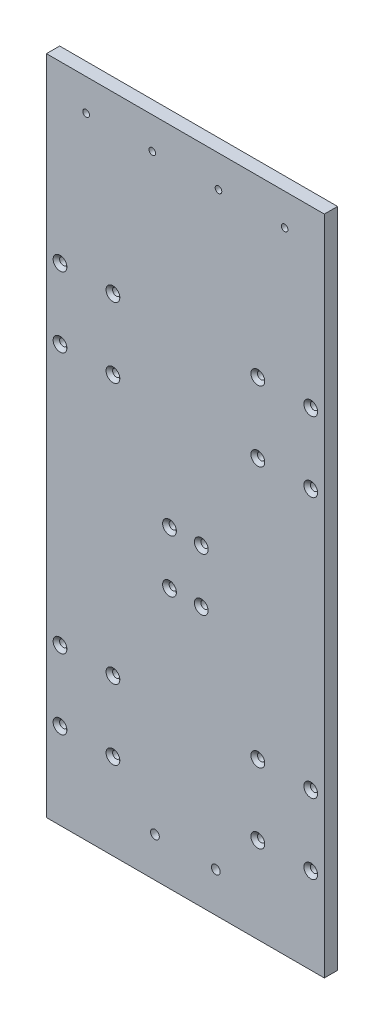
SolidWorks part; units mm, degrees
note: The reader was unsure of these and kept them because the rebuilt part matched: thickness of "Base-Flange1", "Sheet-Metal1", "Sheet-Metal2", "Sheet-Metal3", "Sheet-Metal4", "Sheet-Metal5", "Sheet-Metal6", "Sheet-Metal7", "Sheet-Metal8".
ref_plane "Front Plane" through (0, 0, 0) normal (0, 0, 1) x (1, 0, 0)
ref_plane "Top Plane" through (0, 0, 0) normal (0, 1, 0) x (1, 0, 0)
ref_plane "Right Plane" through (0, 0, 0) normal (1, 0, 0) x (0, 0, -1)
sketch "Sketch1" plane through (0, 0, 0) normal (0, 0, 1) x (1, 0, 0)
  line L1 (-105, -250) -> (105, -250)
  line L2 (-105, -250) -> (-105, 250)
  line L3 (-105, 250) -> (105, 250)
  line L4 (105, -250) -> (105, 250)
  line L5 (-105, -250) -> (105, 250) construction
  line L6 (-105, 250) -> (105, -250) construction
  point P0 (0, 0)
  dimension "D1" = 210
  dimension "D2" = 500
base flange "Base-Flange1" sketch "Sketch1" thickness 10 reverse thickness direction no parameters "D1"=2
sketch "Sketch2" plane through (0, 0, 0) normal (0, 0, 1) x (1, 0, 0)
  line L0 (-74.75, 91.5) -> (74.75, 91.5) construction
  line L1 (-94.75, 65) -> (-54.75, 65) construction
  line L2 (-94.75, 65) -> (-94.75, 118) construction
  line L3 (-94.75, 118) -> (-54.75, 118) construction
  line L4 (-54.75, 65) -> (-54.75, 118) construction
  line L5 (-94.75, 65) -> (-54.75, 118) construction
  line L6 (-94.75, 118) -> (-54.75, 65) construction
  line L7 (54.75, 65) -> (94.75, 65) construction
  line L8 (54.75, 65) -> (54.75, 118) construction
  line L9 (54.75, 118) -> (94.75, 118) construction
  line L10 (94.75, 65) -> (94.75, 118) construction
  line L11 (54.75, 65) -> (94.75, 118) construction
  line L12 (54.75, 118) -> (94.75, 65) construction
  line L13 (-94.75, -185) -> (-54.75, -185) construction
  line L14 (-94.75, -185) -> (-94.75, -132) construction
  line L15 (-94.75, -132) -> (-54.75, -132) construction
  line L16 (-54.75, -185) -> (-54.75, -132) construction
  line L17 (-94.75, -185) -> (-54.75, -132) construction
  line L18 (-94.75, -132) -> (-54.75, -185) construction
  line L19 (54.75, -185) -> (94.75, -185) construction
  line L20 (54.75, -185) -> (54.75, -132) construction
  line L21 (54.75, -132) -> (94.75, -132) construction
  line L22 (94.75, -185) -> (94.75, -132) construction
  line L23 (54.75, -185) -> (94.75, -132) construction
  line L24 (54.75, -132) -> (94.75, -185) construction
  line L25 (74.75, 91.5) -> (74.75, -158.5) construction
  line L26 (74.75, -158.5) -> (-74.75, -158.5) construction
  line L27 (0, 91.5) -> (0, 250) construction
  line L28 (105, 250) -> (-105, 250) construction
  line L29 (-74.75, -158.5) -> (-74.75, 91.5) construction
  circle A0 centre (-94.75, 118) radius 2.75
  circle A1 centre (-94.75, 65) radius 2.75
  circle A2 centre (-54.75, 118) radius 2.75
  circle A3 centre (-54.75, 65) radius 2.75
  circle A4 centre (54.75, 118) radius 2.75
  circle A5 centre (54.75, 65) radius 2.75
  circle A6 centre (94.75, 118) radius 2.75
  circle A7 centre (94.75, 65) radius 2.75
  circle A8 centre (-54.75, -132) radius 2.75
  circle A9 centre (-94.75, -132) radius 2.75
  circle A10 centre (-94.75, -185) radius 2.75
  circle A11 centre (-54.75, -185) radius 2.75
  circle A12 centre (54.75, -132) radius 2.75
  circle A13 centre (94.75, -132) radius 2.75
  circle A14 centre (94.75, -185) radius 2.75
  circle A15 centre (54.75, -185) radius 2.75
  point P0 (-74.75, 91.5)
  point P5 (74.75, 91.5)
  point P10 (-74.75, -158.5)
  point P15 (74.75, -158.5)
  dimension "D3" = 5.5
  dimension "D4" = 189.5
  dimension "D5" = 303
  dimension "D6" = 132
  dimension "D1" = 40
  dimension "D2" = 53
extrude "Cut-Extrude1" cut sketch "Sketch2" against normal blind 10
sketch "Sketch3" plane through (0, 0, 0) normal (0, 0, 1) x (1, 0, 0)
  line L0 (-23, -220) -> (23, -220) construction
  line L1 (0, -220) -> (0, -250) construction
  line L2 (-105, -250) -> (105, -250) construction
  circle A0 centre (-23, -220) radius 3.3
  circle A1 centre (23, -220) radius 3.3
  dimension "D1" = 6.6
  dimension "D2" = 46
  dimension "D3" = 30
extrude "Cut-Extrude2" cut sketch "Sketch3" against normal blind 10
sketch "Sketch4" plane through (0, 0, 0) normal (0, 0, 1) x (1, 0, 0)
  line L0 (-54.75, 65) -> (54.75, 65) construction
  line L1 (54.75, 65) -> (54.75, -132) construction
  line L2 (54.75, -132) -> (-54.75, -132) construction
  line L3 (-54.75, -132) -> (-54.75, 65) construction
  line L4 (0, -33.5) -> (54.75, -33.5) construction
  line L5 (-12, -53.5) -> (12, -53.5) construction
  line L6 (-12, -53.5) -> (-12, -13.5) construction
  line L7 (-12, -13.5) -> (12, -13.5) construction
  line L8 (12, -53.5) -> (12, -13.5) construction
  line L9 (-12, -53.5) -> (12, -13.5) construction
  line L10 (-12, -13.5) -> (12, -53.5) construction
  line L11 (0, -33.5) -> (0, 65) construction
  circle A0 centre (12, -13.5) radius 2.75
  circle A1 centre (12, -53.5) radius 2.75
  circle A2 centre (-12, -53.5) radius 2.75
  circle A3 centre (-12, -13.5) radius 2.75
  point P6 (0, -33.5)
  dimension "D3" = 5.5
  dimension "D1" = 24
  dimension "D2" = 40
extrude "Cut-Extrude3" cut sketch "Sketch4" against normal blind 10
sketch "Sketch5" plane through (0, 0, -10) normal (0, 0, -1) x (-1, 0, 0)
  line L0 (-75, 226) -> (75, 226) construction
  line L1 (0, 226) -> (0, 250) construction
  line L2 (-105, 250) -> (105, 250) construction
  circle A0 centre (-75, 226) radius 1.5
  circle A1 centre (-25, 226) radius 1.5
  circle A2 centre (25, 226) radius 1.5
  circle A3 centre (75, 226) radius 1.5
  dimension "D3" = 3
  dimension "D1" = 150
  dimension "D2" = 24
  dimension "D4" = 50
  dimension "D5" = 50
extrude "Cut-Extrude4" [suppressed] cut sketch "Sketch5" against normal through all
hole_wizard "M6x1.0 Tapped Hole1" positions "Sketch6" profile "Sketch7" tap size "M6x1.0" standard "ANSI Metric"
sketch "Sketch6" plane through (0, 0, -10) normal (0, 0, -1) x (-1, 0, 0)
  point P0 (-75, 226)
  point P3 (-25, 226)
  point P6 (25, 226)
  point P9 (75, 226)
sketch "Sketch7" plane through (75, 226, -10) normal (1, 0, 0) x (0, 1, 0)
  line L0 (0, 0) -> (0, 16.5022)
  line L1 (0, 16.5022) -> (2.5, 15)
  line L2 (2.5, 15) -> (2.5, 0.525)
  line L3 (2.5, 0.525) -> (3.025, 0)
  line L5 (3.025, 0) -> (0, 0)
  line L6 (-2.5, 0.525) -> (-3.025, 0) construction
  line L10 (0, 16.5022) -> (-2.5, 15) construction
  line L11 (0, -6.35) -> (0, 107.95) construction
  dimension "Tap Drill Dia." = 5
  dimension "Tap Drill Depth" = 15
  dimension "Near C'Sink Dia." = 6.05
  dimension "Near C'Sink Angle" = 90
  dimension "Drill Angle" = 118
hole_wizard "CSK for M5 Flat Head Machine Screw1" positions "Sketch8" profile "Sketch9" countersink size "M5" standard "ANSI Metric"
sketch "Sketch8" plane through (0, 0, 0) normal (0, 0, -1) x (-1, 0, 0)
  point P0 (-54.75, 118)
  point P3 (-94.75, 118)
  point P6 (-94.75, 65)
  point P9 (-54.75, 65)
  point P12 (54.75, 118)
  point P15 (94.75, 118)
  point P18 (54.75, 65)
  point P21 (94.75, 65)
  point P24 (-94.75, -132)
  point P27 (-54.75, -132)
  point P30 (-94.75, -185)
  point P33 (-54.75, -185)
  point P36 (54.75, -132)
  point P39 (54.75, -185)
  point P42 (94.75, -132)
  point P45 (94.75, -185)
sketch "Sketch9" plane through (54.75, 118, 0) normal (1, 0, 0) x (0, -1, 0)
  line L0 (0, 0) -> (0, 26.1524)
  line L1 (0, 26.1524) -> (2.75, 24.5)
  line L2 (2.75, 24.5) -> (2.75, 2.45)
  line L3 (2.75, 2.45) -> (5.2, 0)
  line L5 (5.2, 0) -> (0, 0)
  line L6 (-2.75, 2.45) -> (-5.2, 0) construction
  line L10 (0, 26.1524) -> (-2.75, 24.5) construction
  line L11 (0, -6.35) -> (0, 107.95) construction
  dimension "Hole Dia." = 5.5
  dimension "Hole Depth" = 24.5
  dimension "Near C'Sink Dia." = 10.4
  dimension "Near C'Sink Angle" = 90
  dimension "Drill Angle" = 118
hole_wizard "CSK for M5 Flat Head Machine Screw2" positions "Sketch10" profile "Sketch11" countersink size "M5" standard "ANSI Metric"
sketch "Sketch10" plane through (0, 0, 0) normal (0, 0, 1) x (1, 0, 0)
  point P0 (12, -13.5)
  point P3 (-12, -13.5)
  point P6 (-12, -53.5)
  point P9 (12, -53.5)
sketch "Sketch11" plane through (12, -13.5, 0) normal (1, 0, 0) x (0, -1, 0)
  line L0 (0, 0) -> (0, 26.1524)
  line L1 (0, 26.1524) -> (2.75, 24.5)
  line L2 (2.75, 24.5) -> (2.75, 2.45)
  line L3 (2.75, 2.45) -> (5.2, 0)
  line L5 (5.2, 0) -> (0, 0)
  line L6 (-2.75, 2.45) -> (-5.2, 0) construction
  line L10 (0, 26.1524) -> (-2.75, 24.5) construction
  line L11 (0, -6.35) -> (0, 107.95) construction
  dimension "Hole Dia." = 5.5
  dimension "Hole Depth" = 24.5
  dimension "Near C'Sink Dia." = 10.4
  dimension "Near C'Sink Angle" = 90
  dimension "Drill Angle" = 118
sketch "Sketch12" plane through (0, 0, 0) normal (0, 0, 1) x (1, 0, 0)
  line L0 (-70, -187) -> (-70, -207)
  line L1 (-70, -207) -> (-50, -207)
  line L2 (-105, 250) -> (-105, -250) construction
  line L3 (-105, -250) -> (105, -250) construction
  line L4 (0, 0) -> (0, -170.6801) construction
  line L5 (70, -207) -> (50, -207)
  line L6 (70, -187) -> (70, -207)
  dimension "D1" = 35
  dimension "D2" = 43
  dimension "D3" = 20
  dimension "D4" = 20
sketch "Bend-Lines1" [suppressed] plane through (0, 0, 0) normal (0, 1, 0) x (1, 0, 0)
sketch "Bounding-Box1" [suppressed] plane through (0, 0, 0) normal (0, 1, 0) x (1, 0, 0)
sheet metal parameters "Sheet-Metal1" thickness 10 parameters "D1"=2, "D7"=15
flat pattern "Flat-Pattern1" [suppressed]
sketch "Bend-Lines2" plane through (0, 0, 0) normal (0, 1, 0) x (1, 0, 0)
sketch3d "Bounding-Box2" [suppressed]
  line L0 (100, 250, 0) -> (100, -250, 0) construction
  line L1 (-100, 250, 0) -> (-100, -250, 0) construction
  line L2 (100, 250, 0) -> (-100, 250, 0) construction
  line L3 (100, -250, 0) -> (-100, -250, 0) construction
sheet metal parameters "Sheet-Metal2" thickness 10 parameters "D1"=2, "D7"=15
flat pattern "Flat-Pattern1"
sketch "Bend-Lines2" plane through (0, 0, 0) normal (0, 1, 0) x (1, 0, 0)
sketch3d "Bounding-Box2" [suppressed]
  line L0 (105, 250, 0) -> (105, -250, 0) construction
  line L1 (-105, 250, 0) -> (-105, -250, 0) construction
  line L2 (105, 250, 0) -> (-105, 250, 0) construction
  line L3 (105, -250, 0) -> (-105, -250, 0) construction
sheet metal parameters "Sheet-Metal3" thickness 10 parameters "D1"=2, "D7"=15
flat pattern "Flat-Pattern1"
sketch "Bend-Lines2" plane through (0, 0, 0) normal (0, 1, 0) x (1, 0, 0)
sketch3d "Bounding-Box2" [suppressed]
  line L0 (105, 250, 0) -> (105, -250, 0) construction
  line L1 (-105, 250, 0) -> (-105, -250, 0) construction
  line L2 (105, 250, 0) -> (-105, 250, 0) construction
  line L3 (105, -250, 0) -> (-105, -250, 0) construction
sheet metal parameters "Sheet-Metal4" thickness 10 parameters "D1"=2, "D7"=15
flat pattern "Flat-Pattern1" [suppressed]
sketch "Bend-Lines2" plane through (0, 0, 0) normal (0, 1, 0) x (1, 0, 0)
sketch3d "Bounding-Box2" [suppressed]
  line L0 (105, 250, 0) -> (105, -250, 0) construction
  line L1 (-105, 250, 0) -> (-105, -250, 0) construction
  line L2 (105, 250, 0) -> (-105, 250, 0) construction
  line L3 (105, -250, 0) -> (-105, -250, 0) construction
sketch "Sketch5-2" plane through (0, 0, -10) normal (0, 0, -1) x (-1, 0, 0)
  line L0 (-75, 226) -> (75, 226) construction
  line L1 (0, 226) -> (0, 250) construction
  line L2 (-105, 250) -> (105, 250) construction
  circle A0 centre (-75, 226) radius 3 construction
  circle A1 centre (-25, 226) radius 3 construction
  circle A2 centre (25, 226) radius 3 construction
  circle A3 centre (75, 226) radius 3 construction
  dimension "D3" = 6
  dimension "D1" = 150
  dimension "D2" = 24
  dimension "D4" = 50
  dimension "D5" = 50
sheet metal parameters "Sheet-Metal5" thickness 10 parameters "D1"=2, "D7"=15
flat pattern "Flat-Pattern1" [suppressed]
sketch "Bend-Lines2" plane through (0, 0, 0) normal (0, 1, 0) x (1, 0, 0)
sketch3d "Bounding-Box2" [suppressed]
  line L0 (105, 250, 0) -> (105, -250, 0) construction
  line L1 (-105, 250, 0) -> (-105, -250, 0) construction
  line L2 (105, 250, 0) -> (-105, 250, 0) construction
  line L3 (105, -250, 0) -> (-105, -250, 0) construction
sketch "Sketch5-1" [suppressed] plane through (0, 0, -10) normal (0, 0, -1) x (-1, 0, 0)
  line L0 (-75, 226) -> (75, 226) construction
  line L1 (0, 226) -> (0, 250) construction
  line L2 (-105, 250) -> (105, 250) construction
  circle A0 centre (-75, 226) radius 1.5
  circle A1 centre (-25, 226) radius 1.5
  circle A2 centre (25, 226) radius 1.5
  circle A3 centre (75, 226) radius 1.5
  dimension "D3" = 3
  dimension "D1" = 150
  dimension "D2" = 24
  dimension "D4" = 50
  dimension "D5" = 50
sheet metal parameters "Sheet-Metal6" thickness 10 parameters "D1"=2, "D7"=15
flat pattern "Flat-Pattern1" [suppressed]
sketch "Bend-Lines2" plane through (0, 0, 0) normal (0, 1, 0) x (1, 0, 0)
sketch3d "Bounding-Box2" [suppressed]
  line L0 (105, 250, 0) -> (105, -250, 0) construction
  line L1 (-105, 250, 0) -> (-105, -250, 0) construction
  line L2 (105, 250, 0) -> (-105, 250, 0) construction
  line L3 (105, -250, 0) -> (-105, -250, 0) construction
sketch "Sketch5-2" [suppressed] plane through (0, 0, -10) normal (0, 0, -1) x (-1, 0, 0)
  line L0 (-75, 226) -> (75, 226) construction
  line L1 (0, 226) -> (0, 250) construction
  line L2 (-105, 250) -> (105, 250) construction
  circle A0 centre (-75, 226) radius 1.5
  circle A1 centre (-25, 226) radius 1.5
  circle A2 centre (25, 226) radius 1.5
  circle A3 centre (75, 226) radius 1.5
  dimension "D3" = 3
  dimension "D1" = 150
  dimension "D2" = 24
  dimension "D4" = 50
  dimension "D5" = 50
sheet metal parameters "Sheet-Metal7" thickness 10 parameters "D1"=2, "D7"=15
flat pattern "Flat-Pattern1" [suppressed]
sketch "Bend-Lines2" plane through (0, 0, 0) normal (0, 1, 0) x (1, 0, 0)
sketch3d "Bounding-Box2" [suppressed]
  line L0 (105, 250, 0) -> (105, -250, 0) construction
  line L1 (-105, 250, 0) -> (-105, -250, 0) construction
  line L2 (105, 250, 0) -> (-105, 250, 0) construction
  line L3 (105, -250, 0) -> (-105, -250, 0) construction
sketch "Sketch5-1" plane through (0, 0, -10) normal (0, 0, -1) x (-1, 0, 0)
  line L0 (-75, 226) -> (75, 226) construction
  line L1 (0, 226) -> (0, 250) construction
  line L2 (-105, 250) -> (105, 250) construction
  circle A0 centre (-75, 226) radius 1.5
  circle A1 centre (-25, 226) radius 1.5
  circle A2 centre (25, 226) radius 1.5
  circle A3 centre (75, 226) radius 1.5
  dimension "D3" = 3
  dimension "D1" = 150
  dimension "D2" = 24
  dimension "D4" = 50
  dimension "D5" = 50
sheet metal parameters "Sheet-Metal8" thickness 10 parameters "D1"=2, "D7"=15
flat pattern "Flat-Pattern1" [suppressed]
sketch "Bend-Lines2" plane through (0, 0, 0) normal (0, 1, 0) x (1, 0, 0)
sketch3d "Bounding-Box2" [suppressed]
  line L0 (105, 250, 0) -> (105, -250, 0) construction
  line L1 (-105, 250, 0) -> (-105, -250, 0) construction
  line L2 (105, 250, 0) -> (-105, 250, 0) construction
  line L3 (105, -250, 0) -> (-105, -250, 0) construction
sketch "Sketch5-1" plane through (0, 0, -10) normal (0, 0, -1) x (-1, 0, 0)
  line L0 (-75, 226) -> (75, 226) construction
  line L1 (0, 226) -> (0, 250) construction
  line L2 (-105, 250) -> (105, 250) construction
  circle A0 centre (-75, 226) radius 1.5
  circle A1 centre (-25, 226) radius 1.5
  circle A2 centre (25, 226) radius 1.5
  circle A3 centre (75, 226) radius 1.5
  dimension "D3" = 3
  dimension "D1" = 150
  dimension "D2" = 24
  dimension "D4" = 50
  dimension "D5" = 50
